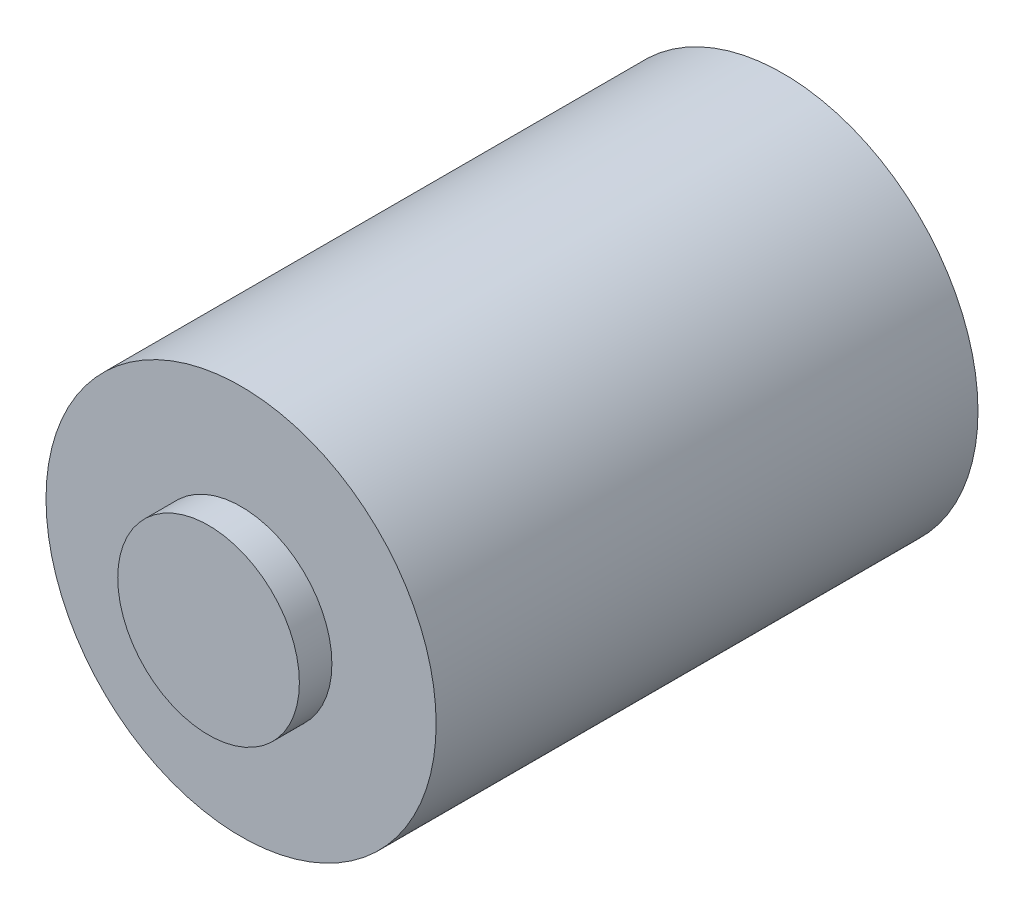
SolidWorks part; units mm, degrees
ref_plane "Front Plane" through (0, 0, 0) normal (0, 0, 1) x (1, 0, 0)
ref_plane "Top Plane" through (0, 0, 0) normal (0, 1, 0) x (1, 0, 0)
ref_plane "Right Plane" through (0, 0, 0) normal (1, 0, 0) x (0, 0, -1)
sketch "Sketch1" plane through (0, 0, 0) normal (0, 0, 1) x (1, 0, 0)
  circle A0 centre (0, 0) radius 18
  dimension "D1" = 36
extrude "Boss-Extrude1" add sketch "Sketch1" along normal blind 50
sketch "Sketch2" plane through (0, 0, 50) normal (0, 0, 1) x (1, 0, 0)
  circle A0 centre (0, 0) radius 8.3808
extrude "Boss-Extrude2" add sketch "Sketch2" along normal blind 3
